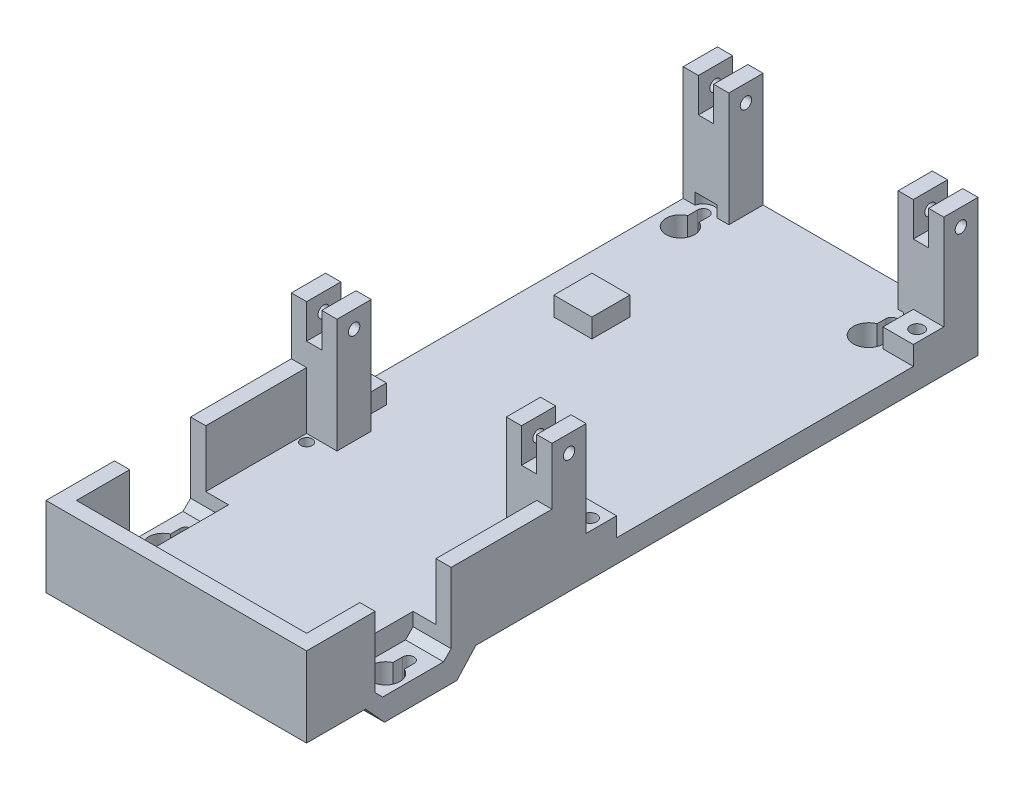
SolidWorks part; units mm, degrees
ref_plane "Front Plane" through (0, 0, 0) normal (0, 0, 1) x (1, 0, 0)
ref_plane "Top Plane" through (0, 0, 0) normal (0, 1, 0) x (1, 0, 0)
ref_plane "Right Plane" through (0, 0, 0) normal (1, 0, 0) x (0, 0, -1)
sketch "Sketch1" plane through (0, 0, 0) normal (0, 1, 0) x (1, 0, 0)
  line L1 (0, 0) -> (-68.5, 0)
  line L2 (0, 0) -> (0, 64.5)
  line L3 (0, 64.5) -> (-68.5, 64.5)
  line L4 (-68.5, 0) -> (-68.5, 64.5)
  dimension "D1" = 64.5
  dimension "D2" = 68.5
extrude "Boss-Extrude3" add sketch "Sketch1" along normal blind 21
sketch "Sketch3" plane through (0, 21, 0) normal (0, 1, 0) x (1, 0, 0)
  line L0 (0, 64.5) -> (-68.5, 64.5) construction
  line L1 (-64.5, 64.5) -> (-4, 64.5)
  line L2 (-64.5, 64.5) -> (-64.5, 4)
  line L3 (-64.5, 4) -> (-4, 4)
  line L4 (-4, 64.5) -> (-4, 4)
  line L5 (-68.5, 64.5) -> (-68.5, 0) construction
  line L6 (-68.5, 0) -> (0, 0) construction
  line L7 (0, 0) -> (0, 64.5) construction
  dimension "D1" = 4
  dimension "D2" = 4
  dimension "D3" = 4
extrude "Cut-Extrude1" cut sketch "Sketch3" against normal blind 15
sketch "Sketch5" plane through (0, 0, -64.5) normal (0, 0, -1) x (-1, 0, 0)
  line L0 (68.5, 21) -> (68.5, 0) construction
  line L1 (0, 0) -> (68.5, 0)
  line L2 (0, 0) -> (0, 6)
  line L3 (0, 6) -> (68.5, 6)
  line L4 (68.5, 0) -> (68.5, 6)
  dimension "D1" = 6
extrude "Boss-Extrude4" add sketch "Sketch5" along normal blind 105
sketch "Sketch9" plane through (0, 21, 0) normal (0, 1, 0) x (1, 0, 0)
  line L0 (-4, 4) -> (-4, 64.5) construction
  line L1 (-4, 38) -> (0, 38)
  line L2 (-4, 38) -> (-4, 18)
  line L3 (-4, 18) -> (0, 18)
  line L4 (0, 38) -> (0, 18)
  line L5 (0, 0) -> (0, 64.5) construction
  line L6 (-4, 64.5) -> (0, 64.5) construction
  dimension "D1" = 20
  dimension "D2" = 26.5
sketch "Sketch10" plane through (0, 0, 0) normal (0, -1, 0) x (1, 0, 0)
  line L0 (0, 0) -> (0, -169.5) construction
  line L1 (0, -15.5) -> (-10, -15.5)
  line L2 (0, -15.5) -> (0, -44.5)
  line L3 (0, -44.5) -> (-10, -44.5)
  line L4 (-10, -15.5) -> (-10, -44.5)
  line L5 (-68.5, 0) -> (0, 0) construction
  dimension "D1" = 15.5
  dimension "D2" = 10
  dimension "D3" = 29
extrude "Boss-Extrude5" add sketch "Sketch10" along normal blind 5.5
extrude "Cut-Extrude2" cut sketch "Sketch9" against normal blind 20.5
sketch "Sketch11" plane through (0, 6, 0) normal (0, 1, 0) x (1, 0, 0)
  line L1 (-4, 38) -> (-10, 38)
  line L2 (-4, 38) -> (-4, 18)
  line L3 (-4, 18) -> (-10, 18)
  line L4 (-10, 38) -> (-10, 18)
  dimension "D1" = 20
  dimension "4" = 6
extrude "Cut-Extrude3" cut sketch "Sketch11" against normal blind 5.5
chamfer "Chamfer2" distance 5.5 distance2 5 2 edges at (-5, -5.5, -44.5) (-5, -5.5, -15.5) first distance on face at (-6.25, -3.4375, -44.5) first distance on face at (-3.75, -3.4375, -15.5)
chamfer "Chamfer3" distance 2 angle 45 2 edges at (-5, 0.5, -38) (-5, 0.5, -18)
sketch "Sketch12" plane through (0, 21, 0) normal (0, 1, 0) x (1, 0, 0)
  line L1 (-68.5, 0) -> (-34.25, 0)
  line L2 (-68.5, 0) -> (-68.5, 169.5)
  line L3 (-68.5, 169.5) -> (-34.25, 169.5)
  line L4 (-34.25, 0) -> (-34.25, 169.5)
  dimension "D1" = 169.5
  dimension "D2" = 34.25
extrude "Cut-Extrude4" cut sketch "Sketch12" against normal blind 50
sketch "Sketch15" plane through (0, 0.5, 0) normal (0, 1, 0) x (1, 0, 0)
  line L0 (0, 20) -> (0, 36) construction
  line L1 (0, 36) -> (-10, 36) construction
  circle A0 centre (-5, 31.7571) radius 1.5
  dimension "D1" = 5
  dimension "D2" = 3
  dimension "D3" = 4.2429
extrude "Cut-Extrude5" cut sketch "Sketch15" against normal blind 50
sketch "Sketch16" plane through (0, 6, 0) normal (0, 1, 0) x (1, 0, 0)
  line L0 (-34.25, 4) -> (-4, 4) construction
  line L1 (-4, 4) -> (-4, 18) construction
  circle A0 centre (-6, 6) radius 1.5
  dimension "D3" = 3
  dimension "D1" = 2
  dimension "D2" = 2
extrude "Cut-Extrude6" cut sketch "Sketch16" against normal blind 50
sketch "Sketch17" plane through (0, 6, 0) normal (0, 1, 0) x (1, 0, 0)
  line L0 (-4, 38) -> (-4, 64.5) construction
  line L1 (-34.25, 4) -> (-4, 4) construction
  circle A0 centre (-6, 62.5) radius 1.5
  dimension "D2" = 3
  dimension "D3" = 58.5
  dimension "D1" = 2
extrude "Cut-Extrude7" cut sketch "Sketch17" against normal blind 50
sketch "Sketch19" plane through (0, 0, -169.5) normal (0, 0, -1) x (-1, 0, 0)
  line L1 (0, 6) -> (34.25, 6)
  line L2 (0, 6) -> (0, 0)
  line L3 (0, 0) -> (34.25, 0)
  line L4 (34.25, 6) -> (34.25, 0)
extrude "Boss-Extrude6" add sketch "Sketch19" along normal blind 7
sketch "Sketch26" plane through (0, 6, 0) normal (0, 1, 0) x (1, 0, 0)
  line L1 (0, 64.5) -> (-12, 64.5)
  line L2 (0, 64.5) -> (0, 73.5)
  line L3 (0, 73.5) -> (-12, 73.5)
  line L4 (-12, 64.5) -> (-12, 73.5)
  dimension "D1" = 9
  dimension "D2" = 12
extrude "Boss-Extrude7" add sketch "Sketch26" along normal blind 30
sketch "Sketch20" plane through (0, 0.5, 0) normal (0, 1, 0) x (1, 0, 0)
  line L0 (0, 20) -> (0, 36) construction
  circle A0 centre (-5, 25.7571) radius 3.75
  circle A2 centre (-5, 31.7571) radius 1.5 construction
  dimension "D1" = 5
  dimension "D2" = 7.5
  dimension "D3" = 6
extrude "Cut-Extrude9" cut sketch "Sketch20" against normal through all
sketch "Sketch21" plane through (0, 0.5, 0) normal (0, 1, 0) x (1, 0, 0)
  line L1 (-6.5, 31.7571) -> (-3.5, 31.7571)
  line L2 (-6.5, 31.7571) -> (-6.5, 29.1941)
  line L3 (-6.5, 29.1941) -> (-3.5, 29.1941)
  line L4 (-3.5, 31.7571) -> (-3.5, 29.1941)
  circle A0 centre (-5, 31.7571) radius 1.5 construction
  circle A1 centre (-5, 25.7571) radius 3.75 construction
  dimension "D1" = 2.5631
extrude "Cut-Extrude10" cut sketch "Sketch21" against normal through all
sketch "Sketch18" plane through (0, 6, 0) normal (0, 1, 0) x (1, 0, 0)
  line L0 (0, 176.5) -> (0, 73.5) construction
  circle A0 centre (-13, 166.7571) radius 1.5
  circle A1 centre (-5, 31.7571) radius 1.5 construction
  dimension "D1" = 135
  dimension "D2" = 3
  dimension "D3" = 13
extrude "Cut-Extrude8" cut sketch "Sketch18" against normal blind 135
sketch "Sketch24" plane through (0, 6, 0) normal (0, 1, 0) x (1, 0, 0)
  circle A0 centre (-13, 160.7571) radius 4
  circle A1 centre (-13, 166.7571) radius 1.5 construction
  circle A2 centre (-13, 166.7571) radius 1.5
  dimension "D2" = 8
  dimension "D1" = 6
extrude "Cut-Extrude13" cut sketch "Sketch24" against normal through all contours A0
sketch "Sketch25" plane through (0, 6, 0) normal (0, 1, 0) x (1, 0, 0)
  line L1 (-14.5, 166.7571) -> (-11.5, 166.7571)
  line L2 (-14.5, 166.7571) -> (-14.5, 164.4652)
  line L3 (-14.5, 164.4652) -> (-11.5, 164.4652)
  line L4 (-11.5, 166.7571) -> (-11.5, 164.4652)
  circle A0 centre (-13, 166.7571) radius 1.5 construction
  circle A1 centre (-13, 160.7571) radius 4 construction
extrude "Cut-Extrude14" cut sketch "Sketch25" against normal through all
sketch "Sketch27" plane through (0, 6, 0) normal (0, 1, 0) x (1, 0, 0)
  line L0 (0, 73.5) -> (-12, 73.5) construction
  line L1 (0, 176.5) -> (0, 73.5) construction
  circle A0 centre (-3, 77.5) radius 1.75
  circle A1 centre (-3, 163.5) radius 1.75
  dimension "D1" = 3.5
  dimension "D3" = 3
  dimension "D4" = 3.5
  dimension "D6" = 3
  dimension "D2" = 4
  dimension "D5" = 86
extrude "Cut-Extrude15" cut sketch "Sketch27" against normal through all
sketch "Sketch30" plane through (0, 6, 0) normal (0, 1, 0) x (1, 0, 0)
  line L1 (0, 73.5) -> (-8, 73.5)
  line L2 (0, 73.5) -> (0, 81.5)
  line L3 (0, 81.5) -> (-8, 81.5)
  line L4 (-8, 73.5) -> (-8, 81.5)
  line L5 (0, 176.5) -> (0, 73.5) construction
  line L7 (0, 159.5) -> (-8, 159.5)
  line L8 (0, 159.5) -> (0, 167.5)
  line L9 (0, 167.5) -> (-8, 167.5)
  line L10 (-8, 159.5) -> (-8, 167.5)
  line L12 (-34.25, 176.5) -> (0, 176.5) construction
  line L13 (0, 73.5) -> (-12, 73.5) construction
  circle A2 centre (-3, 163.5) radius 1.75
  circle A3 centre (-3, 77.5) radius 1.75
  dimension "D4" = 8
  dimension "D6" = 3.5
  dimension "D7" = 3.5
  dimension "D8" = 4
  dimension "D10" = 4
  dimension "D12" = 3
  dimension "D1" = 8
  dimension "D2" = 8
  dimension "D3" = 8
  dimension "D5" = 9
  dimension "D9" = 8
  dimension "D11" = 3
extrude "Boss-Extrude9" add sketch "Sketch30" along normal blind 5
ref_plane "Plane1" through (-34.25, 0, 0) normal (1, 0, 0) x (0, 0, -1)
mirror "Mirror5" about plane through (-34.25, 0, 0) normal (1, 0, 0) of bodies 125
sketch "Sketch31" plane through (0, 11, 0) normal (0, 1, 0) x (1, 0, 0)
  line L1 (-60.5, 159.5) -> (-68.5, 159.5)
  line L2 (-60.5, 159.5) -> (-60.5, 167.5)
  line L3 (-60.5, 167.5) -> (-68.5, 167.5)
  line L4 (-68.5, 159.5) -> (-68.5, 167.5)
extrude "Cut-Extrude16" cut sketch "Sketch31" against normal blind 5
sketch "Sketch32" plane through (0, 6, 0) normal (0, 1, 0) x (1, 0, 0)
  line L1 (-68.5, 176.5) -> (-48.7945, 176.5)
  line L2 (-68.5, 176.5) -> (-68.5, 154.2424)
  line L3 (-68.5, 154.2424) -> (-48.7945, 154.2424)
  line L4 (-48.7945, 176.5) -> (-48.7945, 154.2424)
extrude "Boss-Extrude10" add sketch "Sketch32" against normal blind 6
sketch "Sketch33" plane through (0, 6, 0) normal (0, 1, 0) x (1, 0, 0)
  line L0 (-68.5, 176.5) -> (-68.5, 81.5) construction
  line L1 (-68.5, 176.5) -> (0, 176.5) construction
  circle A0 centre (-62.5, 166.76) radius 1.5
  dimension "D2" = 3
  dimension "D1" = 6
  dimension "D3" = 9.74
extrude "Cut-Extrude17" cut sketch "Sketch33" against normal blind 9.74
sketch "Sketch34" plane through (0, 6, 0) normal (0, 1, 0) x (1, 0, 0)
  line L0 (-68.5, 176.5) -> (-68.5, 81.5) construction
  circle A0 centre (-62.5, 160.76) radius 3.75
  circle A1 centre (-62.5, 166.76) radius 1.5 construction
  dimension "D1" = 6
  dimension "7.5" = 7.5
  dimension "D2" = 6
extrude "Cut-Extrude18" cut sketch "Sketch34" against normal through all
sketch "Sketch36" plane through (0, 0, 0) normal (0, -1, 0) x (1, 0, 0)
  circle A0 centre (-3, -77.5) radius 2.5
  circle A1 centre (-3, -163.5) radius 2.5
  circle A2 centre (-65.5, -77.5) radius 2.5
  dimension "D1" = 5
  dimension "D2" = 5
  dimension "D3" = 5
extrude "Cut-Extrude20" cut sketch "Sketch36" against normal blind 2
sketch "Sketch39" plane through (0, 6, 0) normal (0, 1, 0) x (1, 0, 0)
  line L1 (-61, 166.76) -> (-64, 166.76)
  line L2 (-61, 166.76) -> (-61, 162.5001)
  line L3 (-61, 162.5001) -> (-64, 162.5001)
  line L4 (-64, 166.76) -> (-64, 162.5001)
  circle A0 centre (-62.5, 166.76) radius 1.5 construction
extrude "Cut-Extrude22" cut sketch "Sketch39" against normal through all
sketch "Sketch41" plane through (0, 6, 0) normal (0, 1, 0) x (1, 0, 0)
  line L0 (-68.5, 176.5) -> (0, 176.5) construction
  line L1 (0, 167.5) -> (-12, 167.5)
  line L2 (0, 167.5) -> (0, 176.5)
  line L3 (0, 176.5) -> (-12, 176.5)
  line L4 (-12, 167.5) -> (-12, 176.5)
  line L6 (-68.5, 176.5) -> (-56.5, 176.5)
  line L7 (-68.5, 176.5) -> (-68.5, 167.5)
  line L8 (-68.5, 167.5) -> (-56.5, 167.5)
  line L9 (-56.5, 176.5) -> (-56.5, 167.5)
  dimension "D1" = 12
  dimension "D2" = 12
  dimension "D3" = 9
extrude "Boss-Extrude11" add sketch "Sketch41" along normal blind 30
sketch "Sketch42" plane through (0, 6, 0) normal (0, 1, 0) x (1, 0, 0)
  circle A0 centre (-62.5, 166.76) radius 3
  arc A1 (-61, 166.76) -> (-61.1952, 167.5) centre (-62.5, 166.76) ccw construction
  dimension "D1" = 6
extrude "Cut-Extrude23" cut sketch "Sketch42" along normal blind 3
sketch "Sketch44" plane through (0, 6, 0) normal (0, 1, 0) x (1, 0, 0)
  line L0 (-56.5, 176.5) -> (-12, 176.5) construction
  line L1 (-58.5, 133.5) -> (-48.5, 133.5)
  line L2 (-58.5, 133.5) -> (-58.5, 123.5)
  line L3 (-58.5, 123.5) -> (-48.5, 123.5)
  line L4 (-48.5, 133.5) -> (-48.5, 123.5)
  line L5 (-68.5, 167.5) -> (-68.5, 81.5) construction
  dimension "D1" = 43
  dimension "D2" = 10
  dimension "D3" = 10
  dimension "D4" = 10
extrude "Boss-Extrude12" add sketch "Sketch44" along normal up to vertex (5 mm away) up to point (-60.5, 11, -81.5)
sketch "Sketch46" plane through (0, 36, 0) normal (0, 1, 0) x (1, 0, 0)
  line L0 (-12, 64.5) -> (0, 64.5) construction
  line L1 (-8, 64.5) -> (-4, 64.5)
  line L2 (-8, 64.5) -> (-8, 73.5)
  line L3 (-8, 73.5) -> (-4, 73.5)
  line L4 (-4, 64.5) -> (-4, 73.5)
  line L5 (0, 73.5) -> (-12, 73.5) construction
  line L6 (-56.5, 64.5) -> (-68.5, 64.5) construction
  line L7 (-64.5, 64.5) -> (-60.5, 64.5)
  line L8 (-64.5, 64.5) -> (-64.5, 73.5)
  line L9 (-64.5, 73.5) -> (-60.5, 73.5)
  line L10 (-60.5, 64.5) -> (-60.5, 73.5)
  line L11 (-68.5, 73.5) -> (-56.5, 73.5) construction
  line L12 (-68.5, 167.5) -> (-56.5, 167.5) construction
  line L13 (-64.5, 167.5) -> (-60.5, 167.5)
  line L14 (-64.5, 167.5) -> (-64.5, 176.5)
  line L15 (-64.5, 176.5) -> (-60.5, 176.5)
  line L16 (-60.5, 167.5) -> (-60.5, 176.5)
  line L17 (-56.5, 176.5) -> (-68.5, 176.5) construction
  line L18 (-12, 167.5) -> (0, 167.5) construction
  line L19 (-8, 167.5) -> (-4, 167.5)
  line L20 (-8, 167.5) -> (-8, 176.5)
  line L21 (-8, 176.5) -> (-4, 176.5)
  line L22 (-4, 167.5) -> (-4, 176.5)
  line L23 (0, 176.5) -> (-12, 176.5) construction
  line L24 (-12, 73.5) -> (-12, 64.5) construction
  line L25 (0, 64.5) -> (0, 73.5) construction
  line L26 (-68.5, 64.5) -> (-68.5, 73.5) construction
  line L27 (-56.5, 73.5) -> (-56.5, 64.5) construction
  line L28 (-68.5, 176.5) -> (-68.5, 167.5) construction
  line L29 (-56.5, 167.5) -> (-56.5, 176.5) construction
  line L30 (-12, 176.5) -> (-12, 167.5) construction
  line L31 (0, 167.5) -> (0, 176.5) construction
  point P34 (0, 69)
  dimension "D1" = 4
  dimension "D2" = 4
  dimension "D3" = 4
  dimension "D4" = 4
  dimension "D5" = 4
  dimension "D6" = 4
  dimension "D7" = 4
  dimension "D8" = 4
sketch "Sketch47" plane through (0, 6, 0) normal (0, 1, 0) x (1, 0, 0)
  circle A0 centre (-13, 166.7571) radius 2.5
  arc A1 (-12, 167.8752) -> (-14.5, 166.7571) centre (-13, 166.7571) ccw construction
  dimension "D1" = 5
extrude "Cut-Extrude26" cut sketch "Sketch47" along normal up to vertex (3 mm away) up to point (-65.4073, 9, -167.5)
extrude "Cut-Extrude27" cut sketch "Sketch46" against normal blind 9
sketch "Sketch48" plane through (0, 0, 0) normal (1, 0, 0) x (0, 0, -1)
  line L0 (64.5, 36) -> (73.5, 36) construction
  line L1 (73.5, 36) -> (73.5, 11) construction
  line L2 (167.5, 36) -> (167.5, 11) construction
  line L3 (167.5, 36) -> (176.5, 36) construction
  circle A0 centre (69, 31.5) radius 1.5
  circle A1 centre (172, 31.5) radius 1.5
  dimension "D1" = 4.5
  dimension "D2" = 4.5
  dimension "D3" = 4.5
  dimension "D4" = 4.5
  dimension "D5" = 3
  dimension "D6" = 3
extrude "Cut-Extrude28" cut sketch "Sketch48" against normal up to vertex (68.5 mm away) up to point (-68.5, 6, -167.5)
equation "\"5.5.00mm\"=15"
